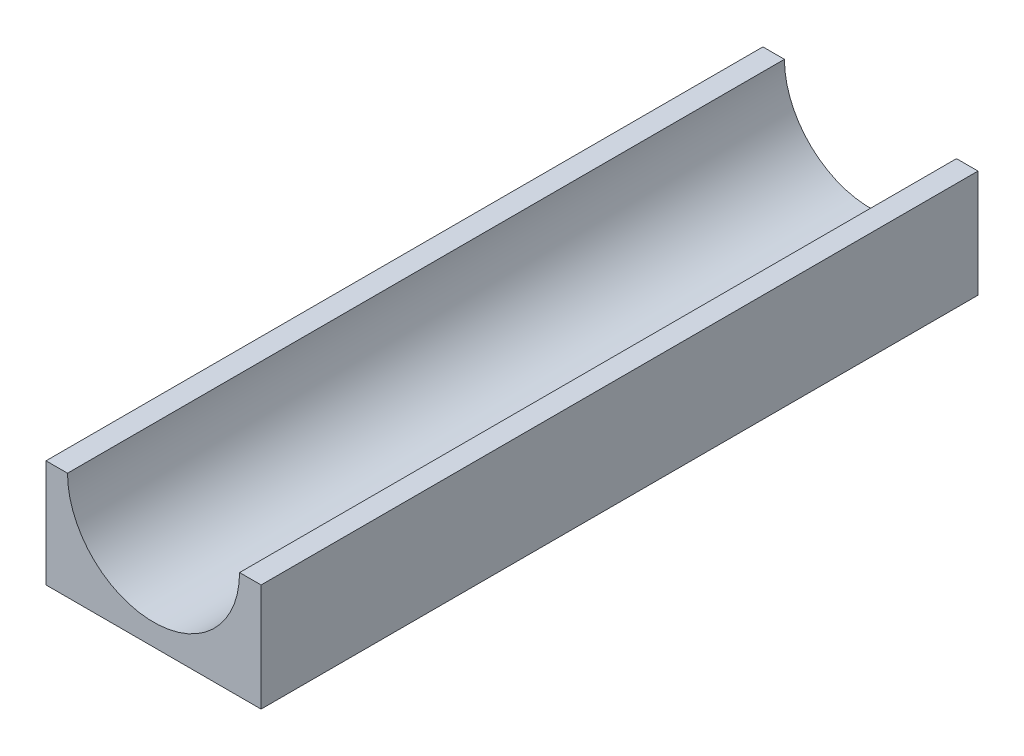
SolidWorks part; units mm, degrees
ref_plane "Front Plane" through (0, 0, 0) normal (0, 0, 1) x (1, 0, 0)
ref_plane "Top Plane" through (0, 0, 0) normal (0, 1, 0) x (1, 0, 0)
ref_plane "Right Plane" through (0, 0, 0) normal (1, 0, 0) x (0, 0, -1)
sketch "Sketch2" plane through (0, 0, 0) normal (0, 0, 1) x (1, 0, 0)
  line L0 (0, 0) -> (-30, 0)
  line L1 (-30, 0) -> (-30, 15)
  line L2 (-30, 15) -> (-27, 15)
  line L3 (0, 15) -> (0, 0)
  line L4 (-3, 15) -> (0, 15)
  arc A0 (-27, 15) -> (-3, 15) centre (-15, 15) ccw
  dimension "D1" = 12
  dimension "D3" = 15
  dimension "D5" = 15
  dimension "D2" = 30
  dimension "D4" = 15
extrude "Boss-Extrude1" add sketch "Sketch2" along normal blind 100
